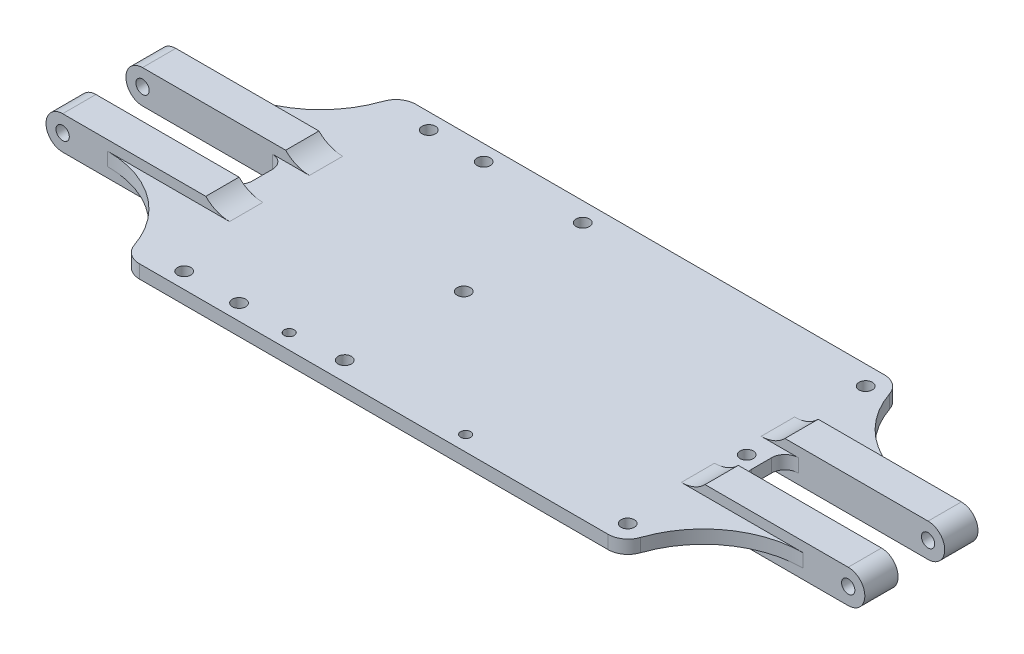
SolidWorks part; units mm, degrees
ref_plane "Front Plane" through (0, 0, 0) normal (0, 0, 1) x (1, 0, 0)
ref_plane "Top Plane" through (0, 0, 0) normal (0, 1, 0) x (1, 0, 0)
ref_plane "Right Plane" through (0, 0, 0) normal (1, 0, 0) x (0, 0, -1)
sketch "Sketch1" plane through (0, 0, 0) normal (0, 1, 0) x (1, 0, 0)
  line L0 (0, 121.3543) -> (0, -121.3543) construction
  line L1 (-75, -41.5) -> (75, -41.5)
  line L2 (-75, -41.5) -> (-75, 41.5)
  line L3 (-75, 41.5) -> (75, 41.5)
  line L4 (75, -41.5) -> (75, 41.5)
  line L5 (-75, -41.5) -> (75, 41.5) construction
  line L6 (-75, 41.5) -> (75, -41.5) construction
  line L7 (-246.33, 0) -> (246.33, 0) construction
  line L8 (-75, 7) -> (-124, 7)
  line L9 (-124, 7) -> (-124, 17)
  line L10 (-124, 17) -> (-75, 17)
  line L11 (-124, -17) -> (-75, -17)
  line L12 (-124, -7) -> (-124, -17)
  line L13 (-75, -7) -> (-124, -7)
  line L14 (-118, 46.0679) -> (-118, -44.6537) construction
  line L15 (124, -17) -> (75, -17)
  line L16 (124, -7) -> (124, -17)
  line L17 (75, -7) -> (124, -7)
  line L18 (75, 7) -> (124, 7)
  line L19 (124, 7) -> (124, 17)
  line L20 (124, 17) -> (75, 17)
  circle A0 centre (70.5, 35.75) radius 2
  circle A1 centre (70.5, 0) radius 2
  circle A2 centre (70.5, -35.75) radius 2
  circle A3 centre (-14.5, -35.75) radius 2
  circle A4 centre (-14.5, 0) radius 2
  circle A5 centre (-14.5, 35.75) radius 2
  circle A6 centre (-30, -36.93) radius 1.5
  circle A7 centre (23, -36.93) radius 1.5
  point P0 (0, 0)
  point P8 (0, 0)
  point P11 (0, 0)
  dimension "D7" = 4
  dimension "D8" = 4
  dimension "D9" = 4
  dimension "D10" = 4
  dimension "D11" = 4
  dimension "D12" = 4
  dimension "D13" = 4.57
  dimension "D15" = 3
  dimension "D16" = 4.57
  dimension "D17" = 3
  dimension "D1" = 83
  dimension "D2" = 150
  dimension "D3" = 14
  dimension "D4" = 10
  dimension "D5" = 43
  dimension "D6" = 6
  dimension "D14" = 45
  dimension "D18" = 98
extrude "Boss-Extrude1" add sketch "Sketch1" along normal mid plane 10 contours L10 L9 L8 L2 | L2 L13 L12 L11 | L19 L20 L4 L18 | L17 L4 L15 L16 region at (-99.5, 0, 12) region at (99.5, 0, 12) region at (-99.5, 0, -12) region at (99.5, 0, -12)
sketch "Sketch2" plane through (0, 0, -17) normal (0, 0, -1) x (-1, 0, 0)
  line L0 (-124, -5) -> (-75, -5) construction
  line L1 (-124, 5) -> (-75, 5) construction
  line L2 (-124, 5) -> (-124, -5) construction
  line L6 (0, 69.849) -> (0, -80.9232) construction
  line L10 (-118, 5) -> (-118, 9.5057)
  line L11 (-118, 9.5057) -> (-152.7264, 9.5057)
  line L12 (-152.7264, 9.5057) -> (-152.7264, -6.9043)
  line L13 (-152.7264, -6.9043) -> (-118, -6.9043)
  line L14 (-118, -6.9043) -> (-118, -5)
  line L15 (118, 5) -> (118, 9.5057)
  line L16 (118, 9.5057) -> (152.7264, 9.5057)
  line L17 (152.7264, 9.5057) -> (152.7264, -6.9043)
  line L18 (152.7264, -6.9043) -> (118, -6.9043)
  line L19 (118, -6.9043) -> (118, -5)
  arc A0 (-118, -5) -> (-118, 5) centre (-118, 0) cw
  circle A1 centre (-118, 0) radius 2
  circle A2 centre (118, 0) radius 2
  arc A3 (118, -5) -> (118, 5) centre (118, 0) ccw
  dimension "D2" = 4
  dimension "D1" = 6
extrude "Cut-Extrude7" cut sketch "Sketch2" against normal through all both and the other way through all
extrude "Boss-Extrude2" add sketch "Sketch1<3>" along normal mid plane 4 contours L1 L4 L3 L2 region at (-0.1668, 0, -0.0422)
sketch "Sketch1<3>" plane through (0, 0, 0) normal (0, 1, 0) x (1, 0, 0) same geometry as "Sketch1"
fillet "Fillet1" radius 10 4 edges at (-75, 2, -12) (-75, 2, 12) (75, 2, -12) (75, 2, 12)
sketch "Sketch3" plane through (0, -2, 0) normal (0, -1, 0) x (1, 0, 0)
  line L0 (-75, 17) -> (75, 17)
  line L1 (-75, 7) -> (75, 7)
  line L2 (-75, -7) -> (75, -7)
  line L3 (-75, -17) -> (75, -17)
  line L4 (-75, -17) -> (-75, -7)
  line L5 (75, -17) -> (75, -7)
  line L6 (75, 7) -> (75, 17)
  line L7 (-75, 7) -> (-75, 17)
extrude "Boss-Extrude3" add sketch "Sketch3" along normal up to surface (3 mm away) up to face at (96.5, -5, 13.25)
fillet "Fillet2" radius 30 4 edges at (-75, 0, 17) (-75, 0, -17) (75, 0, 17) (75, 0, -17)
fillet "Fillet3" radius 4 4 edges at (75, 0, 7) (75, 0, -7) (-75, 0, 7) (-75, 0, -7)
fillet "Fillet4" radius 6 4 edges at (75, 0, 41.5) (-75, 0, 41.5) (75, 0, -41.5) (-75, 0, -41.5)
sketch "Sketch4" plane through (0, 2, 0) normal (0, 1, 0) x (1, 0, 0)
  circle A0 centre (-45.25, -36.75) radius 2
  circle A1 centre (-61.75, -36.75) radius 2
  circle A2 centre (-45.25, 36.75) radius 2
  circle A3 centre (-61.75, 36.75) radius 2
extrude "Cut-Extrude8" cut sketch "Sketch4" against normal through all both and the other way through all
